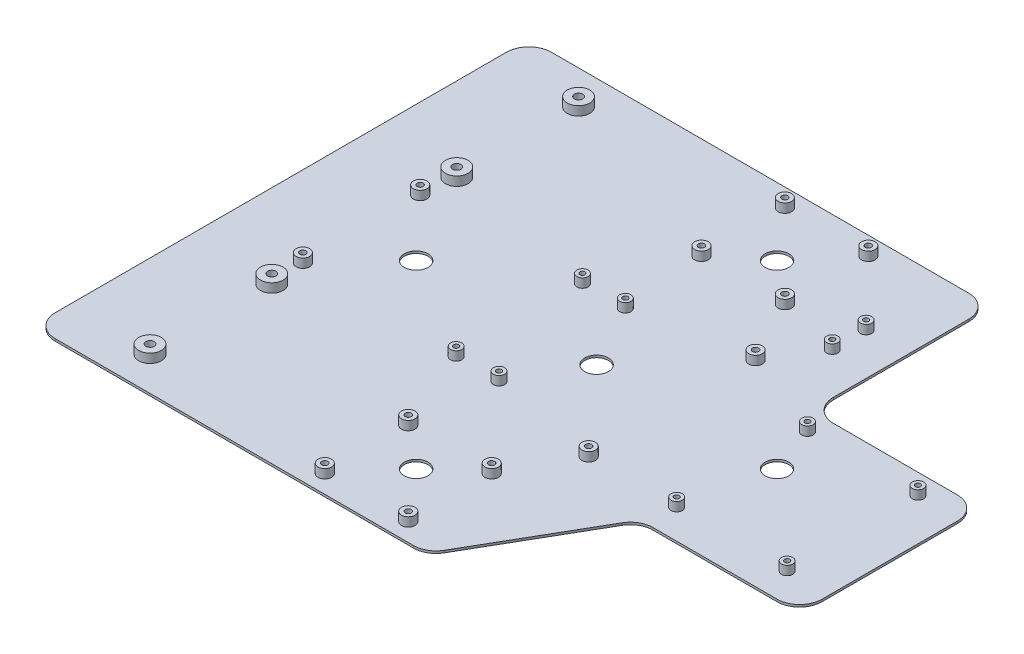
SolidWorks part; units mm, degrees
ref_plane "Front Plane" through (0, 0, 0) normal (0, 0, 1) x (1, 0, 0)
ref_plane "Top Plane" through (0, 0, 0) normal (0, 1, 0) x (1, 0, 0)
ref_plane "Right Plane" through (0, 0, 0) normal (1, 0, 0) x (0, 0, -1)
ref_axis "X" through (-154, 0, 0) along (1, 0, 0)
ref_axis "Y" through (0, 5.25, 0) along (0, -1, 0)
ref_axis "Z" through (0, 0, -121) along (0, 0, 1)
sketch "Sketch1" plane through (0, 0, 0) normal (0, 1, 0) x (1, 0, 0)
  line L0 (-140, 100) -> (-140, -100)
  line L5 (-130, -110) -> (28.812, -110)
  line L6 (37.4722, -105) -> (66.3397, -55)
  line L7 (130, -50) -> (75, -50)
  line L8 (140, -40) -> (140, 20)
  line L9 (130, 30) -> (75, 30)
  line L10 (65, 40) -> (65, 100)
  line L11 (55, 110) -> (-130, 110)
  line L12 (0, 0) -> (-140, 0) construction
  line L13 (0, 0) -> (0, -110) construction
  line L14 (0, 0) -> (140, 0) construction
  circle A0 centre (72.5, 21) radius 1.35 construction
  circle A1 centre (121.5, 21) radius 1.35 construction
  circle A2 centre (121.5, -37) radius 1.35 construction
  circle A3 centre (72.5, -37) radius 1.3 construction
  circle A4 centre (72.5, 21) radius 1.35 construction
  circle A5 centre (121.5, 21) radius 1.35 construction
  circle A6 centre (121.5, -37) radius 1.35 construction
  circle A7 centre (72.5, -37) radius 1.3 construction
  circle A12 centre (18.5, 102) radius 1.5 construction
  circle A13 centre (-18.5, 102) radius 1.5 construction
  circle A14 centre (18.5, 65) radius 1.5 construction
  circle A15 centre (-18.5, 65) radius 1.5 construction
  circle A16 centre (18.5, 102) radius 1.5 construction
  circle A17 centre (-18.5, 102) radius 1.5 construction
  circle A18 centre (18.5, 65) radius 1.5 construction
  circle A19 centre (-18.5, 65) radius 1.5 construction
  circle A20 centre (-15.25, -28) radius 1.25 construction
  circle A21 centre (-34.25, -28) radius 1.25 construction
  circle A22 centre (-15.25, 28) radius 1.25 construction
  circle A23 centre (-34.25, 28) radius 1.25 construction
  circle A24 centre (-15.25, -28) radius 1.25 construction
  circle A25 centre (-34.25, -28) radius 1.25 construction
  circle A26 centre (-15.25, 28) radius 1.25 construction
  circle A27 centre (-34.25, 28) radius 1.25 construction
  circle A28 centre (18.5, -102) radius 1.5 construction
  circle A29 centre (18.5, -65) radius 1.5 construction
  circle A30 centre (-18.5, -102) radius 1.5 construction
  circle A31 centre (-18.5, -65) radius 1.5 construction
  circle A32 centre (18.5, -102) radius 1.5 construction
  circle A33 centre (18.5, -65) radius 1.5 construction
  circle A34 centre (-18.5, -102) radius 1.5 construction
  circle A35 centre (-18.5, -65) radius 1.5 construction
  circle A36 centre (-103, -95) radius 3.25 construction
  circle A37 centre (-103, -41) radius 3.25 construction
  circle A38 centre (-103, -95) radius 3.25 construction
  circle A39 centre (-103, -41) radius 3.25 construction
  circle A40 centre (-103, 95) radius 3.25 construction
  circle A41 centre (-103, 41) radius 3.25 construction
  circle A42 centre (-103, 95) radius 3.25 construction
  circle A43 centre (-103, 41) radius 3.25 construction
  arc A44 (-106.15, 26) -> (-102.25, 26) centre (-104.2, 26) ccw construction
  arc A45 (-102.25, -26) -> (-106.15, -26) centre (-104.2, -26) ccw construction
  arc A46 (-106.15, 26) -> (-102.25, 26) centre (-104.2, 26) ccw construction
  arc A47 (-102.25, -26) -> (-106.15, -26) centre (-104.2, -26) ccw construction
  arc A48 (-106.15, 26) -> (-102.25, 26) centre (-104.2, 26) cw construction
  arc A49 (-106.15, -26) -> (-102.25, -26) centre (-104.2, -26) ccw construction
  circle A50 centre (72.5, -37) radius 1.15
  circle A51 centre (72.5, 21) radius 1.15
  circle A52 centre (121.5, 21) radius 1.15
  circle A53 centre (121.5, -37) radius 1.15
  circle A54 centre (18.5, -65) radius 1.35
  circle A55 centre (18.5, -102) radius 1.35
  circle A56 centre (-18.5, -102) radius 1.35
  circle A57 centre (-18.5, -65) radius 1.35
  circle A58 centre (-15.25, -28) radius 1.15
  circle A59 centre (-34.25, -28) radius 1.15
  circle A60 centre (-34.25, 28) radius 1.15
  circle A61 centre (-15.25, 28) radius 1.15
  circle A62 centre (18.5, 65) radius 1.35
  circle A63 centre (-18.5, 65) radius 1.35
  circle A64 centre (-18.5, 102) radius 1.35
  circle A65 centre (18.5, 102) radius 1.35
  circle A66 centre (46.5, 58) radius 1.15
  circle A67 centre (46.5, 73) radius 1.15
  circle A68 centre (-103, 95) radius 1.85
  circle A69 centre (-103, 41) radius 1.85
  circle A70 centre (-103, -41) radius 1.85
  circle A71 centre (-104.2, -26) radius 1.35
  circle A72 centre (-104.2, 26) radius 1.35
  circle A73 centre (-103, -95) radius 1.85
  circle A74 centre (72.5, -37) radius 2.5
  circle A75 centre (72.5, 21) radius 2.5
  circle A76 centre (121.5, 21) radius 2.5
  circle A77 centre (121.5, -37) radius 2.5
  circle A78 centre (46.5, 58) radius 2.5
  circle A79 centre (46.5, 73) radius 2.5
  circle A80 centre (18.5, 65) radius 3
  circle A81 centre (18.5, 102) radius 3
  circle A82 centre (-18.5, 102) radius 3
  circle A83 centre (-18.5, 65) radius 3
  circle A84 centre (-15.25, 28) radius 2.5
  circle A85 centre (-34.25, 28) radius 2.5
  circle A86 centre (-34.25, -28) radius 2.5
  circle A87 centre (-15.25, -28) radius 2.5
  circle A88 centre (-18.5, -65) radius 3
  circle A89 centre (-18.5, -102) radius 3
  circle A90 centre (18.5, -65) radius 3
  circle A91 centre (18.5, -102) radius 3
  circle A92 centre (-103, -95) radius 5
  circle A93 centre (-103, -41) radius 5
  circle A94 centre (-104.2, -26) radius 3
  circle A95 centre (-104.2, 26) radius 3
  circle A96 centre (-103, 41) radius 5
  circle A97 centre (-103, 95) radius 5
  circle A98 centre (33.5, 37) radius 1.7 construction
  circle A99 centre (33.5, -37) radius 1.7 construction
  circle A100 centre (33.5, 37) radius 1.7 construction
  circle A101 centre (33.5, -37) radius 1.7 construction
  circle A102 centre (33.5, -37) radius 1.35
  circle A103 centre (33.5, 37) radius 1.35
  circle A104 centre (33.5, 37) radius 3
  circle A105 centre (33.5, -37) radius 3
  arc A106 (-140, -100) -> (-130, -110) centre (-130, -100) ccw
  arc A107 (28.812, -110) -> (37.4722, -105) centre (28.812, -100) ccw
  arc A108 (66.3397, -55) -> (75, -50) centre (75, -60) cw
  arc A109 (130, -50) -> (140, -40) centre (130, -40) ccw
  arc A110 (140, 20) -> (130, 30) centre (130, 20) ccw
  arc A111 (75, 30) -> (65, 40) centre (75, 40) cw
  arc A112 (65, 100) -> (55, 110) centre (55, 100) ccw
  arc A113 (-130, 110) -> (-140, 100) centre (-130, 100) ccw
  circle A114 centre (0, -80) radius 5 construction
  circle A115 centre (0, 80) radius 5 construction
  circle A116 centre (80, 0) radius 5 construction
  circle A117 centre (0, 0) radius 5 construction
  circle A118 centre (-80, 0) radius 5 construction
  circle A119 centre (0, -80) radius 5 construction
  circle A120 centre (0, 80) radius 5 construction
  circle A121 centre (80, 0) radius 5 construction
  circle A122 centre (0, 0) radius 5 construction
  circle A123 centre (-80, 0) radius 5 construction
  circle A124 centre (-80, 0) radius 5.25
  circle A125 centre (0, 80) radius 5.25
  circle A126 centre (0, 0) radius 5.25
  circle A127 centre (80, 0) radius 5.25
  circle A128 centre (0, -80) radius 5.25
  circle A129 centre (46.5, 73) radius 1.25 construction
  circle A130 centre (46.5, 58) radius 1.25 construction
  circle A131 centre (46.5, 73) radius 1.25 construction
  circle A132 centre (46.5, 58) radius 1.25 construction
  dimension "D1" = 2.3
  dimension "D2" = 2.7
  dimension "D3" = 3.7
  dimension "D4" = 5
  dimension "D5" = 6
  dimension "D6" = 10
  dimension "D8" = 140
  dimension "D7" = 140
  dimension "D13" = 10
  dimension "D9" = 50
  dimension "D10" = 30
  dimension "D11" = 65
  dimension "D12" = 110
  dimension "D14" = 120
  dimension "D15" = 0.25
extrude "Boss-Extrude1" add sketch "Sketch1" along normal up to surface (5 mm away) contours A92 A73 | A89 A56 | A91 A55 | A90 A54 | A88 A57 | A74 A50 | A77 A53 | A76 A52 | A75 A51 | A78 A66 | A79 A67 | A82 A64 | A81 A65 | A80 A62 | A83 A63 | A97 A68 | A96 A69 | A95 A72 | A94 A71 | A93 A70 | A87 A58 | A86 A59 | A85 A60 | A84 A61 | A105 A102 | A104 A103 region at (70.0707, 0, 37) region at (70.0707, 0, -21) region at (119.0707, 0, -21) region at (119.0707, 0, 37) region at (44.0707, 0, -58) region at (44.0707, 0, -73) region at (15.5849, 0, -65) region at (15.5849, 0, -102) region at (-21.4151, 0, -102) region at (-21.4151, 0, -65) region at (-17.6793, 0, -28) region at (-36.6793, 0, -28) region at (-36.6793, 0, 28) region at (-17.6793, 0, 28) region at (-21.4151, 0, 65) region at (-21.4151, 0, 102) region at (15.5849, 0, 65) region at (15.5849, 0, 102) region at (-107.8586, 0, 95) region at (-107.8586, 0, 41) region at (-107.1151, 0, 26) region at (-107.1151, 0, -26) region at (-107.8586, 0, -41) region at (-107.8586, 0, -95) region at (30.5849, 0, -37) region at (30.5849, 0, 37)
extrude "Boss-Extrude2" add sketch "Sketch1<4>" along normal blind 1 contours A93 A92 | A88 | A91 A90 A88 A89 | A77 L0 A76 A75 A74 | A79 A78 | A83 | A83 A80 A81 A82 | A97 A96 | A87 A84 A85 A86 | A95 A94 | A96 A95 | A94 A93 region at (-22.2701, 0, -0.2129)
sketch "Sketch1<4>" plane through (0, 0, 0) normal (0, 1, 0) x (1, 0, 0) same geometry as "Sketch1"
